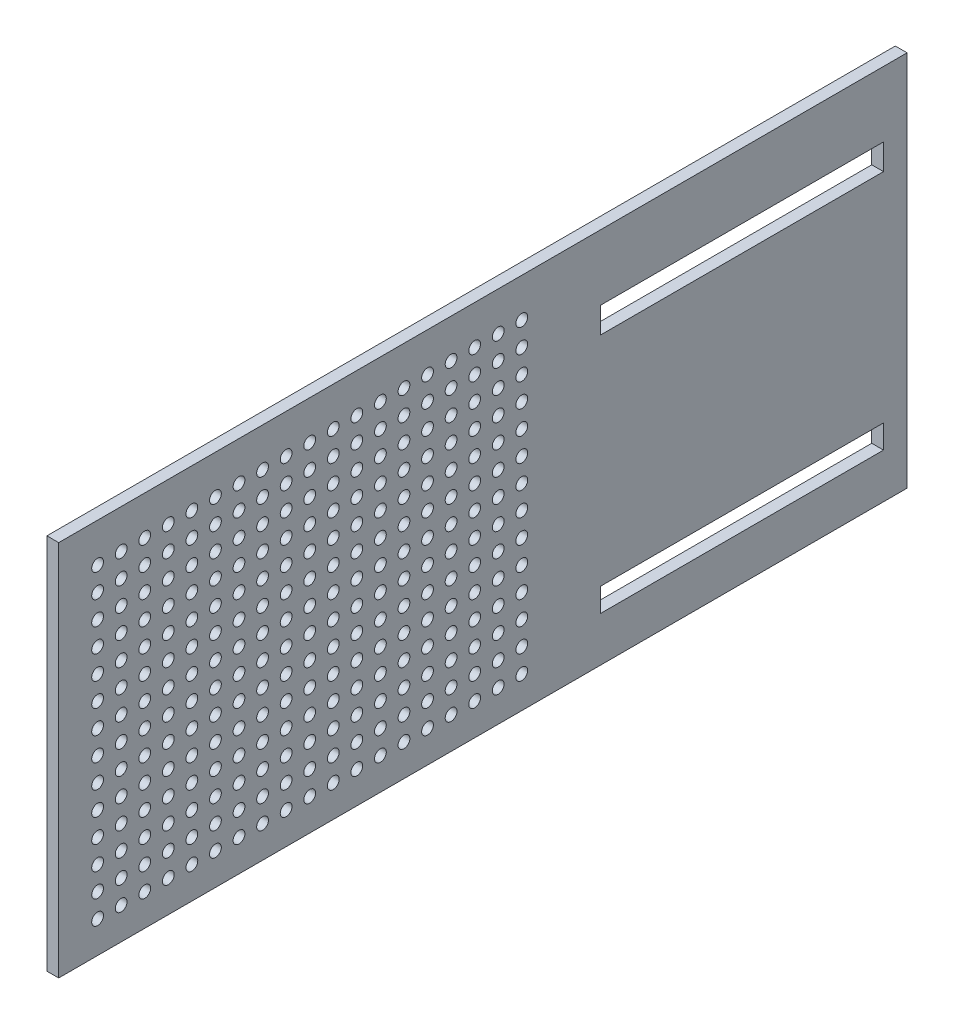
SolidWorks part; units mm, degrees
ref_plane "Front Plane" through (0, 0, 0) normal (0, 0, 1) x (1, 0, 0)
ref_plane "Top Plane" through (0, 0, 0) normal (0, 1, 0) x (1, 0, 0)
ref_plane "Right Plane" through (0, 0, 0) normal (1, 0, 0) x (0, 0, -1)
sketch "Sketch1" plane through (0, 0, 0) normal (0, 0, 1) x (1, 0, 0)
  line L0 (1.5875, 47.625) -> (36.5125, 47.625)
  line L1 (1.5875, -50.8) -> (-1.5875, -50.8)
  line L2 (1.5875, -50.8) -> (1.5875, 47.625)
  line L4 (-1.5875, -50.8) -> (-1.5875, 50.8)
  line L5 (1.5875, -50.8) -> (-1.5875, 50.8) construction
  line L6 (3.5127, 112.4075) -> (-1.5875, -50.8) construction
  line L7 (-1.5875, 50.8) -> (36.5125, 50.8)
  line L10 (36.5125, 50.8) -> (36.5125, 47.625)
  point P0 (0, 0)
  point P7 (0, -50.8)
  dimension "D1" = 3.175
  dimension "D2" = 3.175
  dimension "D3" = 38.1
  dimension "D4" = 101.6
extrude "Boss-Extrude1" add sketch "Sketch1" along normal blind 228.6
sketch "Sketch2" plane through (1.5875, 0, 0) normal (1, 0, 0) x (0, 0, -1)
  line L0 (-228.6, -29.4596) -> (0, 47.625) construction
  line L1 (-228.6, -50.8) -> (-228.6, 47.625) construction
  line L2 (-228.6, 47.625) -> (0, 47.625) construction
  line L3 (0, -50.8) -> (0, 47.625) construction
ref_plane "Plane1 - BACKBOARD PLANE" through (0, 42.7626, 14.4197) normal (0, -0.9476, -0.3195) x (0, 0.3195, -0.9476)
ref_plane "Plane1" through (0, -1.5875, 0) normal (0, -1, 0) x (-1, 0, 0)
sketch "Sketch3" plane through (-1.5875, 0, 0) normal (-1, 0, 0) x (0, 0, 1)
  line L0 (228.6, -50.8) -> (0, -50.8) construction
  line L1 (82.55, -32.385) -> (6.35, -32.385)
  line L2 (82.55, -32.385) -> (82.55, -38.735)
  line L3 (82.55, -38.735) -> (6.35, -38.735)
  line L4 (6.35, -32.385) -> (6.35, -38.735)
  line L5 (82.55, -32.385) -> (6.35, -38.735) construction
  line L6 (82.55, -38.735) -> (6.35, -32.385) construction
  line L7 (0, 50.8) -> (0, -50.8) construction
  line L18 (6.35, 33.1888) -> (82.55, 33.1888)
  line L19 (6.35, 33.1888) -> (6.35, 26.2472)
  line L20 (6.35, 26.2472) -> (82.55, 26.2472)
  line L21 (82.55, 33.1888) -> (82.55, 26.2472)
  point P0 (44.45, -35.56)
  point P13 (6.35, 29.718)
  point P14 (6.35, -35.56)
  dimension "D1" = 6.35
  dimension "D2" = 15.24
  dimension "D3" = 76.2
  dimension "D4" = 6.35
  dimension "D5" = 65.278
extrude "Cut-Extrude1" cut sketch "Sketch3" against normal up to next
sketch "Sketch4" plane through (-1.5875, 0, 0) normal (-1, 0, 0) x (0, 0, 1)
  circle A0 centre (103.8185, 40.3289) radius 1.5875
  circle A1 centre (110.1685, 40.3289) radius 1.5875
  circle A2 centre (116.5185, 40.3289) radius 1.5875
  circle A3 centre (122.8685, 40.3289) radius 1.5875
  circle A4 centre (129.2185, 40.3289) radius 1.5875
  circle A5 centre (110.1685, 33.9789) radius 1.5875
  circle A6 centre (116.5185, 33.9789) radius 1.5875
  circle A7 centre (122.8685, 33.9789) radius 1.5875
  circle A8 centre (129.2185, 33.9789) radius 1.5875
  circle A9 centre (110.1685, 27.6289) radius 1.5875
  circle A10 centre (116.5185, 27.6289) radius 1.5875
  circle A11 centre (122.8685, 27.6289) radius 1.5875
  circle A12 centre (129.2185, 27.6289) radius 1.5875
  circle A13 centre (110.1685, 21.2789) radius 1.5875
  circle A14 centre (116.5185, 21.2789) radius 1.5875
  circle A15 centre (122.8685, 21.2789) radius 1.5875
  circle A16 centre (129.2185, 21.2789) radius 1.5875
  circle A17 centre (103.8185, 33.9789) radius 1.5875
  circle A18 centre (103.8185, 27.6289) radius 1.5875
  circle A19 centre (103.8185, 21.2789) radius 1.5875
  circle A20 centre (135.5685, 40.3289) radius 1.5875
  circle A21 centre (141.9185, 40.3289) radius 1.5875
  circle A22 centre (148.2685, 40.3289) radius 1.5875
  circle A23 centre (154.6185, 40.3289) radius 1.5875
  circle A24 centre (160.9685, 40.3289) radius 1.5875
  circle A25 centre (167.3185, 40.3289) radius 1.5875
  circle A26 centre (173.6685, 40.3289) radius 1.5875
  circle A27 centre (180.0185, 40.3289) radius 1.5875
  circle A28 centre (186.3685, 40.3289) radius 1.5875
  circle A29 centre (192.7185, 40.3289) radius 1.5875
  circle A30 centre (199.0685, 40.3289) radius 1.5875
  circle A31 centre (205.4185, 40.3289) radius 1.5875
  circle A32 centre (211.7685, 40.3289) radius 1.5875
  circle A33 centre (218.1185, 40.3289) radius 1.5875
  circle A34 centre (135.5685, 33.9789) radius 1.5875
  circle A35 centre (141.9185, 33.9789) radius 1.5875
  circle A36 centre (148.2685, 33.9789) radius 1.5875
  circle A37 centre (154.6185, 33.9789) radius 1.5875
  circle A38 centre (160.9685, 33.9789) radius 1.5875
  circle A39 centre (167.3185, 33.9789) radius 1.5875
  circle A40 centre (173.6685, 33.9789) radius 1.5875
  circle A41 centre (180.0185, 33.9789) radius 1.5875
  circle A42 centre (186.3685, 33.9789) radius 1.5875
  circle A43 centre (192.7185, 33.9789) radius 1.5875
  circle A44 centre (199.0685, 33.9789) radius 1.5875
  circle A45 centre (205.4185, 33.9789) radius 1.5875
  circle A46 centre (211.7685, 33.9789) radius 1.5875
  circle A47 centre (218.1185, 33.9789) radius 1.5875
  circle A48 centre (135.5685, 27.6289) radius 1.5875
  circle A49 centre (141.9185, 27.6289) radius 1.5875
  circle A50 centre (148.2685, 27.6289) radius 1.5875
  circle A51 centre (154.6185, 27.6289) radius 1.5875
  circle A52 centre (160.9685, 27.6289) radius 1.5875
  circle A53 centre (167.3185, 27.6289) radius 1.5875
  circle A54 centre (173.6685, 27.6289) radius 1.5875
  circle A55 centre (180.0185, 27.6289) radius 1.5875
  circle A56 centre (186.3685, 27.6289) radius 1.5875
  circle A57 centre (192.7185, 27.6289) radius 1.5875
  circle A58 centre (199.0685, 27.6289) radius 1.5875
  circle A59 centre (205.4185, 27.6289) radius 1.5875
  circle A60 centre (211.7685, 27.6289) radius 1.5875
  circle A61 centre (218.1185, 27.6289) radius 1.5875
  circle A62 centre (135.5685, 21.2789) radius 1.5875
  circle A63 centre (141.9185, 21.2789) radius 1.5875
  circle A64 centre (148.2685, 21.2789) radius 1.5875
  circle A65 centre (154.6185, 21.2789) radius 1.5875
  circle A66 centre (160.9685, 21.2789) radius 1.5875
  circle A67 centre (167.3185, 21.2789) radius 1.5875
  circle A68 centre (173.6685, 21.2789) radius 1.5875
  circle A69 centre (180.0185, 21.2789) radius 1.5875
  circle A70 centre (186.3685, 21.2789) radius 1.5875
  circle A71 centre (192.7185, 21.2789) radius 1.5875
  circle A72 centre (199.0685, 21.2789) radius 1.5875
  circle A73 centre (205.4185, 21.2789) radius 1.5875
  circle A74 centre (211.7685, 21.2789) radius 1.5875
  circle A75 centre (218.1185, 21.2789) radius 1.5875
  circle A76 centre (103.8185, 14.9289) radius 1.5875
  circle A77 centre (110.1685, 14.9289) radius 1.5875
  circle A78 centre (116.5185, 14.9289) radius 1.5875
  circle A79 centre (122.8685, 14.9289) radius 1.5875
  circle A80 centre (129.2185, 14.9289) radius 1.5875
  circle A81 centre (135.5685, 14.9289) radius 1.5875
  circle A82 centre (141.9185, 14.9289) radius 1.5875
  circle A83 centre (148.2685, 14.9289) radius 1.5875
  circle A84 centre (154.6185, 14.9289) radius 1.5875
  circle A85 centre (160.9685, 14.9289) radius 1.5875
  circle A86 centre (167.3185, 14.9289) radius 1.5875
  circle A87 centre (173.6685, 14.9289) radius 1.5875
  circle A88 centre (180.0185, 14.9289) radius 1.5875
  circle A89 centre (186.3685, 14.9289) radius 1.5875
  circle A90 centre (192.7185, 14.9289) radius 1.5875
  circle A91 centre (199.0685, 14.9289) radius 1.5875
  circle A92 centre (205.4185, 14.9289) radius 1.5875
  circle A93 centre (211.7685, 14.9289) radius 1.5875
  circle A94 centre (218.1185, 14.9289) radius 1.5875
  circle A95 centre (103.8185, 8.5789) radius 1.5875
  circle A96 centre (110.1685, 8.5789) radius 1.5875
  circle A97 centre (116.5185, 8.5789) radius 1.5875
  circle A98 centre (122.8685, 8.5789) radius 1.5875
  circle A99 centre (129.2185, 8.5789) radius 1.5875
  circle A100 centre (135.5685, 8.5789) radius 1.5875
  circle A101 centre (141.9185, 8.5789) radius 1.5875
  circle A102 centre (148.2685, 8.5789) radius 1.5875
  circle A103 centre (154.6185, 8.5789) radius 1.5875
  circle A104 centre (160.9685, 8.5789) radius 1.5875
  circle A105 centre (167.3185, 8.5789) radius 1.5875
  circle A106 centre (173.6685, 8.5789) radius 1.5875
  circle A107 centre (180.0185, 8.5789) radius 1.5875
  circle A108 centre (186.3685, 8.5789) radius 1.5875
  circle A109 centre (192.7185, 8.5789) radius 1.5875
  circle A110 centre (199.0685, 8.5789) radius 1.5875
  circle A111 centre (205.4185, 8.5789) radius 1.5875
  circle A112 centre (211.7685, 8.5789) radius 1.5875
  circle A113 centre (218.1185, 8.5789) radius 1.5875
  circle A114 centre (103.8185, 2.2289) radius 1.5875
  circle A115 centre (110.1685, 2.2289) radius 1.5875
  circle A116 centre (116.5185, 2.2289) radius 1.5875
  circle A117 centre (122.8685, 2.2289) radius 1.5875
  circle A118 centre (129.2185, 2.2289) radius 1.5875
  circle A119 centre (135.5685, 2.2289) radius 1.5875
  circle A120 centre (141.9185, 2.2289) radius 1.5875
  circle A121 centre (148.2685, 2.2289) radius 1.5875
  circle A122 centre (154.6185, 2.2289) radius 1.5875
  circle A123 centre (160.9685, 2.2289) radius 1.5875
  circle A124 centre (167.3185, 2.2289) radius 1.5875
  circle A125 centre (173.6685, 2.2289) radius 1.5875
  circle A126 centre (180.0185, 2.2289) radius 1.5875
  circle A127 centre (186.3685, 2.2289) radius 1.5875
  circle A128 centre (192.7185, 2.2289) radius 1.5875
  circle A129 centre (199.0685, 2.2289) radius 1.5875
  circle A130 centre (205.4185, 2.2289) radius 1.5875
  circle A131 centre (211.7685, 2.2289) radius 1.5875
  circle A132 centre (218.1185, 2.2289) radius 1.5875
  circle A133 centre (103.8185, -4.1211) radius 1.5875
  circle A134 centre (110.1685, -4.1211) radius 1.5875
  circle A135 centre (116.5185, -4.1211) radius 1.5875
  circle A136 centre (122.8685, -4.1211) radius 1.5875
  circle A137 centre (129.2185, -4.1211) radius 1.5875
  circle A138 centre (135.5685, -4.1211) radius 1.5875
  circle A139 centre (141.9185, -4.1211) radius 1.5875
  circle A140 centre (148.2685, -4.1211) radius 1.5875
  circle A141 centre (154.6185, -4.1211) radius 1.5875
  circle A142 centre (160.9685, -4.1211) radius 1.5875
  circle A143 centre (167.3185, -4.1211) radius 1.5875
  circle A144 centre (173.6685, -4.1211) radius 1.5875
  circle A145 centre (180.0185, -4.1211) radius 1.5875
  circle A146 centre (186.3685, -4.1211) radius 1.5875
  circle A147 centre (192.7185, -4.1211) radius 1.5875
  circle A148 centre (199.0685, -4.1211) radius 1.5875
  circle A149 centre (205.4185, -4.1211) radius 1.5875
  circle A150 centre (211.7685, -4.1211) radius 1.5875
  circle A151 centre (218.1185, -4.1211) radius 1.5875
  circle A152 centre (103.8185, -10.4711) radius 1.5875
  circle A153 centre (110.1685, -10.4711) radius 1.5875
  circle A154 centre (116.5185, -10.4711) radius 1.5875
  circle A155 centre (122.8685, -10.4711) radius 1.5875
  circle A156 centre (129.2185, -10.4711) radius 1.5875
  circle A157 centre (135.5685, -10.4711) radius 1.5875
  circle A158 centre (141.9185, -10.4711) radius 1.5875
  circle A159 centre (148.2685, -10.4711) radius 1.5875
  circle A160 centre (154.6185, -10.4711) radius 1.5875
  circle A161 centre (160.9685, -10.4711) radius 1.5875
  circle A162 centre (167.3185, -10.4711) radius 1.5875
  circle A163 centre (173.6685, -10.4711) radius 1.5875
  circle A164 centre (180.0185, -10.4711) radius 1.5875
  circle A165 centre (186.3685, -10.4711) radius 1.5875
  circle A166 centre (192.7185, -10.4711) radius 1.5875
  circle A167 centre (199.0685, -10.4711) radius 1.5875
  circle A168 centre (205.4185, -10.4711) radius 1.5875
  circle A169 centre (211.7685, -10.4711) radius 1.5875
  circle A170 centre (218.1185, -10.4711) radius 1.5875
  circle A171 centre (103.8185, -16.8211) radius 1.5875
  circle A172 centre (110.1685, -16.8211) radius 1.5875
  circle A173 centre (116.5185, -16.8211) radius 1.5875
  circle A174 centre (122.8685, -16.8211) radius 1.5875
  circle A175 centre (129.2185, -16.8211) radius 1.5875
  circle A176 centre (135.5685, -16.8211) radius 1.5875
  circle A177 centre (141.9185, -16.8211) radius 1.5875
  circle A178 centre (148.2685, -16.8211) radius 1.5875
  circle A179 centre (154.6185, -16.8211) radius 1.5875
  circle A180 centre (160.9685, -16.8211) radius 1.5875
  circle A181 centre (167.3185, -16.8211) radius 1.5875
  circle A182 centre (173.6685, -16.8211) radius 1.5875
  circle A183 centre (180.0185, -16.8211) radius 1.5875
  circle A184 centre (186.3685, -16.8211) radius 1.5875
  circle A185 centre (192.7185, -16.8211) radius 1.5875
  circle A186 centre (199.0685, -16.8211) radius 1.5875
  circle A187 centre (205.4185, -16.8211) radius 1.5875
  circle A188 centre (211.7685, -16.8211) radius 1.5875
  circle A189 centre (218.1185, -16.8211) radius 1.5875
  circle A190 centre (103.8185, -23.1711) radius 1.5875
  circle A191 centre (110.1685, -23.1711) radius 1.5875
  circle A192 centre (116.5185, -23.1711) radius 1.5875
  circle A193 centre (122.8685, -23.1711) radius 1.5875
  circle A194 centre (129.2185, -23.1711) radius 1.5875
  circle A195 centre (135.5685, -23.1711) radius 1.5875
  circle A196 centre (141.9185, -23.1711) radius 1.5875
  circle A197 centre (148.2685, -23.1711) radius 1.5875
  circle A198 centre (154.6185, -23.1711) radius 1.5875
  circle A199 centre (160.9685, -23.1711) radius 1.5875
  circle A200 centre (167.3185, -23.1711) radius 1.5875
  circle A201 centre (173.6685, -23.1711) radius 1.5875
  circle A202 centre (180.0185, -23.1711) radius 1.5875
  circle A203 centre (186.3685, -23.1711) radius 1.5875
  circle A204 centre (192.7185, -23.1711) radius 1.5875
  circle A205 centre (199.0685, -23.1711) radius 1.5875
  circle A206 centre (205.4185, -23.1711) radius 1.5875
  circle A207 centre (211.7685, -23.1711) radius 1.5875
  circle A208 centre (218.1185, -23.1711) radius 1.5875
  circle A209 centre (103.8185, -29.5211) radius 1.5875
  circle A210 centre (110.1685, -29.5211) radius 1.5875
  circle A211 centre (116.5185, -29.5211) radius 1.5875
  circle A212 centre (122.8685, -29.5211) radius 1.5875
  circle A213 centre (129.2185, -29.5211) radius 1.5875
  circle A214 centre (135.5685, -29.5211) radius 1.5875
  circle A215 centre (141.9185, -29.5211) radius 1.5875
  circle A216 centre (148.2685, -29.5211) radius 1.5875
  circle A217 centre (154.6185, -29.5211) radius 1.5875
  circle A218 centre (160.9685, -29.5211) radius 1.5875
  circle A219 centre (167.3185, -29.5211) radius 1.5875
  circle A220 centre (173.6685, -29.5211) radius 1.5875
  circle A221 centre (180.0185, -29.5211) radius 1.5875
  circle A222 centre (186.3685, -29.5211) radius 1.5875
  circle A223 centre (192.7185, -29.5211) radius 1.5875
  circle A224 centre (199.0685, -29.5211) radius 1.5875
  circle A225 centre (205.4185, -29.5211) radius 1.5875
  circle A226 centre (211.7685, -29.5211) radius 1.5875
  circle A227 centre (218.1185, -29.5211) radius 1.5875
  circle A228 centre (103.8185, -35.8711) radius 1.5875
  circle A229 centre (110.1685, -35.8711) radius 1.5875
  circle A230 centre (116.5185, -35.8711) radius 1.5875
  circle A231 centre (122.8685, -35.8711) radius 1.5875
  circle A232 centre (129.2185, -35.8711) radius 1.5875
  circle A233 centre (135.5685, -35.8711) radius 1.5875
  circle A234 centre (141.9185, -35.8711) radius 1.5875
  circle A235 centre (148.2685, -35.8711) radius 1.5875
  circle A236 centre (154.6185, -35.8711) radius 1.5875
  circle A237 centre (160.9685, -35.8711) radius 1.5875
  circle A238 centre (167.3185, -35.8711) radius 1.5875
  circle A239 centre (173.6685, -35.8711) radius 1.5875
  circle A240 centre (180.0185, -35.8711) radius 1.5875
  circle A241 centre (186.3685, -35.8711) radius 1.5875
  circle A242 centre (192.7185, -35.8711) radius 1.5875
  circle A243 centre (199.0685, -35.8711) radius 1.5875
  circle A244 centre (205.4185, -35.8711) radius 1.5875
  circle A245 centre (211.7685, -35.8711) radius 1.5875
  circle A246 centre (218.1185, -35.8711) radius 1.5875
  circle A247 centre (103.8185, -42.2211) radius 1.5875
  circle A248 centre (110.1685, -42.2211) radius 1.5875
  circle A249 centre (116.5185, -42.2211) radius 1.5875
  circle A250 centre (122.8685, -42.2211) radius 1.5875
  circle A251 centre (129.2185, -42.2211) radius 1.5875
  circle A252 centre (135.5685, -42.2211) radius 1.5875
  circle A253 centre (141.9185, -42.2211) radius 1.5875
  circle A254 centre (148.2685, -42.2211) radius 1.5875
  circle A255 centre (154.6185, -42.2211) radius 1.5875
  circle A256 centre (160.9685, -42.2211) radius 1.5875
  circle A257 centre (167.3185, -42.2211) radius 1.5875
  circle A258 centre (173.6685, -42.2211) radius 1.5875
  circle A259 centre (180.0185, -42.2211) radius 1.5875
  circle A260 centre (186.3685, -42.2211) radius 1.5875
  circle A261 centre (192.7185, -42.2211) radius 1.5875
  circle A262 centre (199.0685, -42.2211) radius 1.5875
  circle A263 centre (205.4185, -42.2211) radius 1.5875
  circle A264 centre (211.7685, -42.2211) radius 1.5875
  circle A265 centre (218.1185, -42.2211) radius 1.5875
  dimension "D1" = 3.175
  dimension "D2" = 19
  dimension "D3" = 14
extrude "Cut-Extrude2" cut sketch "Sketch4" against normal up to next (3.175 mm away)
sketch "Sketch5" plane through (0, 50.8, 0) normal (0, 1, 0) x (1, 0, 0)
  line L0 (36.5125, 0) -> (-1.5875, 0) construction
  line L1 (18.7325, -5.08) -> (12.1285, -5.08)
  line L2 (18.7325, -5.08) -> (18.7325, -157.48)
  line L3 (18.7325, -157.48) -> (12.1285, -157.48)
  line L4 (12.1285, -5.08) -> (12.1285, -157.48)
  line L5 (36.5125, -228.6) -> (36.5125, 0) construction
  point P8 (15.4305, -5.08)
  dimension "D1" = 6.604
  dimension "D2" = 152.4
  dimension "D3" = 5.08
  dimension "D4" = 21.082
extrude "Cut-Extrude3" cut sketch "Sketch5" against normal up to next
sketch "Sketch6" plane through (0, 50.8, 0) normal (0, 1, 0) x (1, 0, 0)
  line L0 (36.5125, -228.6) -> (-1.5875, -228.6) construction
  line L1 (36.5125, -228.6) -> (36.5125, 0) construction
  circle A0 centre (6.0325, -222.25) radius 1.5875
  circle A1 centre (12.3825, -222.25) radius 1.5875
  circle A2 centre (18.7325, -222.25) radius 1.5875
  circle A3 centre (25.0825, -222.25) radius 1.5875
  circle A4 centre (31.4325, -222.25) radius 1.5875
  circle A5 centre (12.3825, -215.9) radius 1.5875
  circle A6 centre (18.7325, -215.9) radius 1.5875
  circle A7 centre (25.0825, -215.9) radius 1.5875
  circle A8 centre (31.4325, -215.9) radius 1.5875
  circle A9 centre (12.3825, -209.55) radius 1.5875
  circle A10 centre (18.7325, -209.55) radius 1.5875
  circle A11 centre (25.0825, -209.55) radius 1.5875
  circle A12 centre (31.4325, -209.55) radius 1.5875
  circle A13 centre (12.3825, -203.2) radius 1.5875
  circle A14 centre (18.7325, -203.2) radius 1.5875
  circle A15 centre (25.0825, -203.2) radius 1.5875
  circle A16 centre (31.4325, -203.2) radius 1.5875
  circle A17 centre (12.3825, -196.85) radius 1.5875
  circle A18 centre (18.7325, -196.85) radius 1.5875
  circle A19 centre (25.0825, -196.85) radius 1.5875
  circle A20 centre (31.4325, -196.85) radius 1.5875
  circle A21 centre (12.3825, -190.5) radius 1.5875
  circle A22 centre (18.7325, -190.5) radius 1.5875
  circle A23 centre (25.0825, -190.5) radius 1.5875
  circle A24 centre (31.4325, -190.5) radius 1.5875
  circle A25 centre (12.3825, -184.15) radius 1.5875
  circle A26 centre (18.7325, -184.15) radius 1.5875
  circle A27 centre (25.0825, -184.15) radius 1.5875
  circle A28 centre (31.4325, -184.15) radius 1.5875
  circle A29 centre (12.3825, -177.8) radius 1.5875
  circle A30 centre (18.7325, -177.8) radius 1.5875
  circle A31 centre (25.0825, -177.8) radius 1.5875
  circle A32 centre (31.4325, -177.8) radius 1.5875
  circle A33 centre (12.3825, -171.45) radius 1.5875
  circle A34 centre (18.7325, -171.45) radius 1.5875
  circle A35 centre (25.0825, -171.45) radius 1.5875
  circle A36 centre (31.4325, -171.45) radius 1.5875
  circle A37 centre (12.3825, -165.1) radius 1.5875
  circle A38 centre (18.7325, -165.1) radius 1.5875
  circle A39 centre (25.0825, -165.1) radius 1.5875
  circle A40 centre (31.4325, -165.1) radius 1.5875
  circle A43 centre (25.0825, -158.75) radius 1.5875
  circle A44 centre (31.4325, -158.75) radius 1.5875
  circle A47 centre (25.0825, -152.4) radius 1.5875
  circle A48 centre (31.4325, -152.4) radius 1.5875
  circle A51 centre (25.0825, -146.05) radius 1.5875
  circle A52 centre (31.4325, -146.05) radius 1.5875
  circle A55 centre (25.0825, -139.7) radius 1.5875
  circle A56 centre (31.4325, -139.7) radius 1.5875
  circle A59 centre (25.0825, -133.35) radius 1.5875
  circle A60 centre (31.4325, -133.35) radius 1.5875
  circle A63 centre (25.0825, -127) radius 1.5875
  circle A64 centre (31.4325, -127) radius 1.5875
  circle A67 centre (25.0825, -120.65) radius 1.5875
  circle A68 centre (31.4325, -120.65) radius 1.5875
  circle A71 centre (25.0825, -114.3) radius 1.5875
  circle A72 centre (31.4325, -114.3) radius 1.5875
  circle A75 centre (25.0825, -107.95) radius 1.5875
  circle A76 centre (31.4325, -107.95) radius 1.5875
  circle A79 centre (25.0825, -101.6) radius 1.5875
  circle A80 centre (31.4325, -101.6) radius 1.5875
  circle A83 centre (25.0825, -95.25) radius 1.5875
  circle A84 centre (31.4325, -95.25) radius 1.5875
  circle A87 centre (25.0825, -88.9) radius 1.5875
  circle A88 centre (31.4325, -88.9) radius 1.5875
  circle A91 centre (25.0825, -82.55) radius 1.5875
  circle A92 centre (31.4325, -82.55) radius 1.5875
  circle A95 centre (25.0825, -76.2) radius 1.5875
  circle A96 centre (31.4325, -76.2) radius 1.5875
  circle A99 centre (25.0825, -69.85) radius 1.5875
  circle A100 centre (31.4325, -69.85) radius 1.5875
  circle A103 centre (25.0825, -63.5) radius 1.5875
  circle A104 centre (31.4325, -63.5) radius 1.5875
  circle A107 centre (25.0825, -57.15) radius 1.5875
  circle A108 centre (31.4325, -57.15) radius 1.5875
  circle A111 centre (25.0825, -50.8) radius 1.5875
  circle A112 centre (31.4325, -50.8) radius 1.5875
  circle A115 centre (25.0825, -44.45) radius 1.5875
  circle A116 centre (31.4325, -44.45) radius 1.5875
  circle A119 centre (25.0825, -38.1) radius 1.5875
  circle A120 centre (31.4325, -38.1) radius 1.5875
  circle A121 centre (6.0325, -215.9) radius 1.5875
  circle A122 centre (6.0325, -209.55) radius 1.5875
  circle A123 centre (6.0325, -203.2) radius 1.5875
  circle A124 centre (6.0325, -196.85) radius 1.5875
  circle A125 centre (6.0325, -190.5) radius 1.5875
  circle A126 centre (6.0325, -184.15) radius 1.5875
  circle A127 centre (6.0325, -177.8) radius 1.5875
  circle A128 centre (6.0325, -171.45) radius 1.5875
  circle A129 centre (6.0325, -165.1) radius 1.5875
  circle A130 centre (6.0325, -158.75) radius 1.5875
  circle A131 centre (6.0325, -152.4) radius 1.5875
  circle A132 centre (6.0325, -146.05) radius 1.5875
  circle A133 centre (6.0325, -139.7) radius 1.5875
  circle A134 centre (6.0325, -133.35) radius 1.5875
  circle A135 centre (6.0325, -127) radius 1.5875
  circle A136 centre (6.0325, -120.65) radius 1.5875
  circle A137 centre (6.0325, -114.3) radius 1.5875
  circle A138 centre (6.0325, -107.95) radius 1.5875
  circle A139 centre (6.0325, -101.6) radius 1.5875
  circle A140 centre (6.0325, -95.25) radius 1.5875
  circle A141 centre (6.0325, -88.9) radius 1.5875
  circle A142 centre (6.0325, -82.55) radius 1.5875
  circle A143 centre (6.0325, -76.2) radius 1.5875
  circle A144 centre (6.0325, -69.85) radius 1.5875
  circle A145 centre (6.0325, -63.5) radius 1.5875
  circle A146 centre (6.0325, -57.15) radius 1.5875
  circle A147 centre (6.0325, -50.8) radius 1.5875
  circle A148 centre (6.0325, -44.45) radius 1.5875
  circle A149 centre (6.0325, -38.1) radius 1.5875
  circle A150 centre (18.7325, -50.8) radius 1.5875 [skipped]
  circle A151 centre (12.3825, -44.45) radius 1.5875 [skipped]
  circle A152 centre (18.7325, -44.45) radius 1.5875 [skipped]
  circle A153 centre (12.3825, -38.1) radius 1.5875 [skipped]
  circle A154 centre (18.7325, -38.1) radius 1.5875 [skipped]
  circle A155 centre (12.3825, -63.5) radius 1.5875 [skipped]
  circle A156 centre (18.7325, -63.5) radius 1.5875 [skipped]
  circle A157 centre (12.3825, -57.15) radius 1.5875 [skipped]
  circle A158 centre (18.7325, -57.15) radius 1.5875 [skipped]
  circle A159 centre (12.3825, -50.8) radius 1.5875 [skipped]
  circle A160 centre (12.3825, -158.75) radius 1.5875 [skipped]
  circle A161 centre (18.7325, -158.75) radius 1.5875 [skipped]
  circle A162 centre (12.3825, -152.4) radius 1.5875 [skipped]
  circle A163 centre (18.7325, -152.4) radius 1.5875 [skipped]
  circle A164 centre (12.3825, -146.05) radius 1.5875 [skipped]
  circle A165 centre (18.7325, -146.05) radius 1.5875 [skipped]
  circle A166 centre (12.3825, -139.7) radius 1.5875 [skipped]
  circle A167 centre (18.7325, -139.7) radius 1.5875 [skipped]
  circle A168 centre (12.3825, -133.35) radius 1.5875 [skipped]
  circle A169 centre (18.7325, -133.35) radius 1.5875 [skipped]
  circle A170 centre (12.3825, -127) radius 1.5875 [skipped]
  circle A171 centre (18.7325, -127) radius 1.5875 [skipped]
  circle A172 centre (12.3825, -120.65) radius 1.5875 [skipped]
  circle A173 centre (18.7325, -120.65) radius 1.5875 [skipped]
  circle A174 centre (12.3825, -114.3) radius 1.5875 [skipped]
  circle A175 centre (18.7325, -114.3) radius 1.5875 [skipped]
  circle A176 centre (12.3825, -107.95) radius 1.5875 [skipped]
  circle A177 centre (18.7325, -107.95) radius 1.5875 [skipped]
  circle A178 centre (12.3825, -101.6) radius 1.5875 [skipped]
  circle A179 centre (18.7325, -101.6) radius 1.5875 [skipped]
  circle A180 centre (12.3825, -95.25) radius 1.5875 [skipped]
  circle A181 centre (18.7325, -95.25) radius 1.5875 [skipped]
  circle A182 centre (12.3825, -88.9) radius 1.5875 [skipped]
  circle A183 centre (18.7325, -88.9) radius 1.5875 [skipped]
  circle A184 centre (12.3825, -82.55) radius 1.5875 [skipped]
  circle A185 centre (18.7325, -82.55) radius 1.5875 [skipped]
  circle A186 centre (12.3825, -76.2) radius 1.5875 [skipped]
  circle A187 centre (18.7325, -76.2) radius 1.5875 [skipped]
  circle A188 centre (12.3825, -69.85) radius 1.5875 [skipped]
  circle A189 centre (18.7325, -69.85) radius 1.5875 [skipped]
  dimension "D1" = 3.175
  dimension "D2" = 6.35
  dimension "D3" = 30.48
  dimension "D4" = 5
  dimension "D5" = 30
extrude "Cut-Extrude4" cut sketch "Sketch6" against normal up to next (3.175 mm away)
ref_plane "Plane2" through (1.5875, 0, 0) normal (1, 0, 0) x (0, 0, -1)
sketch "Sketch7" plane through (0, 0, 228.6) normal (0, 0, 1) x (1, 0, 0)
  line L0 (36.5125, 50.8) -> (-1.5875, 50.8) construction
  line L1 (1.5875, 50.8) -> (36.5125, 50.8)
  line L2 (1.5875, 50.8) -> (1.5875, 47.625)
  line L3 (1.5875, 47.625) -> (36.5125, 47.625)
  line L4 (36.5125, 50.8) -> (36.5125, 47.625)
  line L5 (1.5875, -54.1337) -> (1.5875, 54.1337) construction
  line L6 (36.5125, 47.625) -> (36.5125, 50.8) construction
  line L7 (1.5875, 47.625) -> (36.5125, 47.625) construction
extrude "Cut-Extrude5" cut sketch "Sketch7" against normal through all
equation "\"eighthinch\"= 0.125"
equation "\"D2@Sketch1\"=\"eighthinch\""
